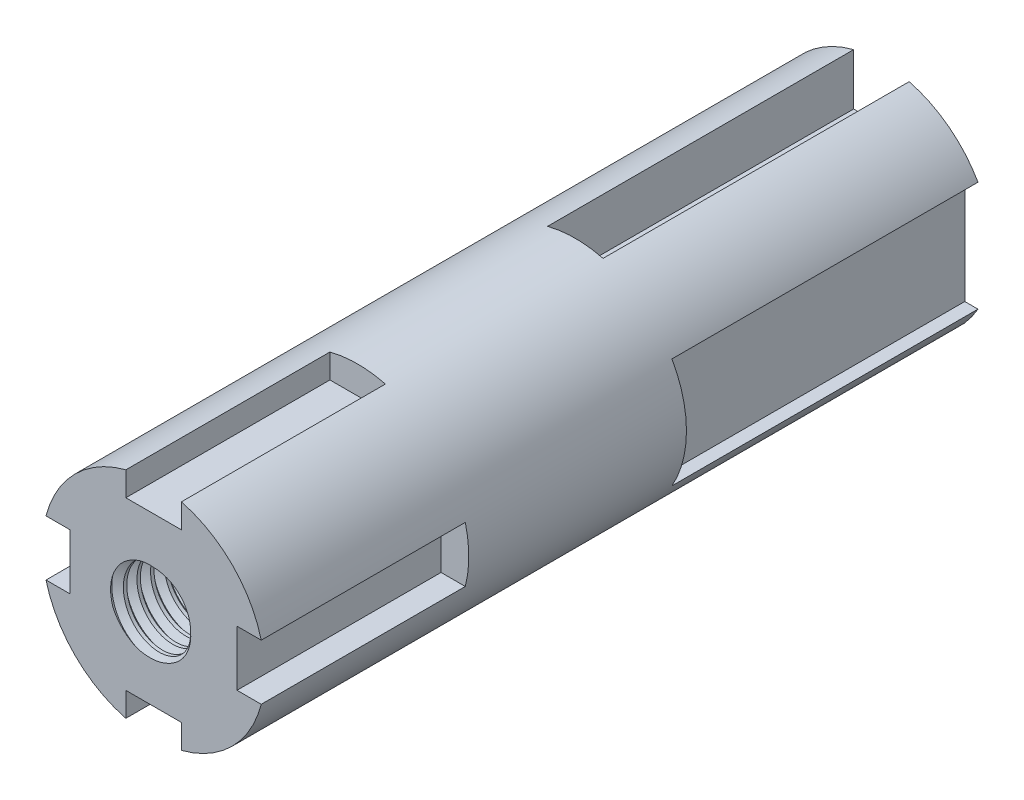
SolidWorks part; units mm, degrees
ref_plane "Front Plane" through (0, 0, 0) normal (0, 0, 1) x (1, 0, 0)
ref_plane "Top Plane" through (0, 0, 0) normal (0, 1, 0) x (1, 0, 0)
ref_plane "Right Plane" through (0, 0, 0) normal (1, 0, 0) x (0, 0, -1)
sketch "Sketch3" plane through (0, 0, 0) normal (0, 0, 1) x (1, 0, 0)
  circle A0 centre (0, 0) radius 4.085
  dimension "D1" = 8.17
extrude "Boss-Extrude2" add sketch "Sketch3" along normal blind 26.75
sketch "Sketch6" plane through (0, 0, 26.75) normal (0, 0, 1) x (1, 0, 0)
  line L10 (4.085, 1.02) -> (3.065, 1.02)
  line L11 (-1.02, 4.085) -> (1.02, 4.085)
  line L12 (-1.02, 4.085) -> (-1.02, 3.065)
  line L13 (-1.02, 3.065) -> (1.02, 3.065)
  line L14 (1.02, 4.085) -> (1.02, 3.065)
  line L15 (4.085, 1.02) -> (4.085, -1.02)
  line L16 (4.085, -1.02) -> (3.065, -1.02)
  line L17 (3.065, 1.02) -> (3.065, -1.02)
  line L18 (1.02, -4.085) -> (1.02, -3.065)
  line L19 (1.02, -4.085) -> (-1.02, -4.085)
  line L20 (-1.02, -4.085) -> (-1.02, -3.065)
  line L21 (1.02, -3.065) -> (-1.02, -3.065)
  line L22 (-4.085, -1.02) -> (-3.065, -1.02)
  line L23 (-4.085, -1.02) -> (-4.085, 1.02)
  line L24 (-4.085, 1.02) -> (-3.065, 1.02)
  line L25 (-3.065, -1.02) -> (-3.065, 1.02)
  circle A2 centre (0, 0) radius 4.085 construction
  point P4 (0, 4.085)
  point P23 (0, 0)
  dimension "D1" = 2.04
  dimension "D2" = 1.02
  dimension "D3" = 4
extrude "Cut-Extrude1" cut sketch "Sketch6" against normal blind 7.5
sketch "Sketch4" plane through (0, 0, 0) normal (0, 0, -1) x (-1, 0, 0)
  line L5 (-1.02, 2.065) -> (1.02, 2.065)
  line L6 (-1.02, 2.065) -> (-1.02, 4.085)
  line L7 (-1.02, 4.085) -> (1.02, 4.085)
  line L8 (1.02, 2.065) -> (1.02, 4.085)
  line L9 (-3.065, -2.02) -> (-4.085, -2.02)
  line L10 (-3.065, -2.02) -> (-3.065, 2.02)
  line L11 (-3.065, 2.02) -> (-4.085, 2.02)
  line L12 (-4.085, -2.02) -> (-4.085, 2.02)
  line L13 (-3.065, -2.02) -> (-4.085, 2.02) construction
  line L14 (-3.065, 2.02) -> (-4.085, -2.02) construction
  line L15 (3.065, -2.02) -> (4.085, -2.02)
  line L16 (3.065, -2.02) -> (3.065, 2.02)
  line L17 (3.065, 2.02) -> (4.085, 2.02)
  line L18 (4.085, -2.02) -> (4.085, 2.02)
  line L19 (3.065, -2.02) -> (4.085, 2.02) construction
  line L20 (3.065, 2.02) -> (4.085, -2.02) construction
  circle A2 centre (0, 0) radius 4.085 construction
  point P4 (0, 4.085)
  point P6 (-3.575, 0)
  point P13 (3.575, 0)
  dimension "D1" = 2.02
  dimension "D2" = 2.04
  dimension "D3" = 1.02
  dimension "D4" = 4.04
extrude "Cut-Extrude2" cut sketch "Sketch4" against normal blind 11.25
sketch "Sketch7" plane through (0, 0, 0) normal (0, 0, -1) x (-1, 0, 0)
  circle A0 centre (0, 0) radius 1.36
  dimension "D1" = 2.72
extrude "Cut-Extrude3" cut sketch "Sketch7" against normal blind 5
sketch "Sketch8" plane through (0, 0, 26.75) normal (0, 0, 1) x (1, 0, 0)
  circle A0 centre (0, 0) radius 1.36
  dimension "D1" = 2.72
extrude "Cut-Extrude4" cut sketch "Sketch8" against normal blind 5
thread "Thread1" pitch 0.5 method cut profile "Thread Profile1" start angle 0, offset 0, length 10, pitch 0.5, diameter 2.72
ref_plane "Plane1" through (-1.36, 0, 5) normal (0, -1, 0) x (-1, 0, 0)
sketch "Thread Profile1" plane through (-1.36, 0, 5) normal (0, -1, 0) x (-1, 0, 0)
  line L0 (0, 0) -> (0, 0.5) construction
  line L1 (0, 0) -> (0.2706, 0.1562)
  line L2 (0.2706, 0.1562) -> (0.2706, 0.2187)
  line L3 (0.2706, 0.2187) -> (0, 0.375)
  line L4 (0.2706, 0.1875) -> (0, 0.1875) construction
  line L11 (0, 0) -> (0, 0.375)
  point P2 (0, 0)
  dimension "Pitch" = 0.5
  dimension "Profile_Angle" = 60
  dimension "Profile_Land" = 0.0625
  dimension "Profile_Height" = 0.2706
thread "Thread2" pitch 0.5 method cut profile "Thread Profile2" start angle 0, offset 0, length 10, pitch 0.5, diameter 2.72
ref_plane "Plane2" through (1.36, 0, 21.75) normal (0, -1, 0) x (1, 0, 0)
sketch "Thread Profile2" plane through (1.36, 0, 21.75) normal (0, -1, 0) x (1, 0, 0)
  line L0 (0, 0) -> (0, 0.5) construction
  line L1 (0, 0) -> (0.2706, 0.1562)
  line L2 (0.2706, 0.1562) -> (0.2706, 0.2187)
  line L3 (0.2706, 0.2187) -> (0, 0.375)
  line L4 (0.2706, 0.1875) -> (0, 0.1875) construction
  line L11 (0, 0) -> (0, 0.375)
  point P2 (0, 0)
  dimension "Pitch" = 0.5
  dimension "Profile_Angle" = 60
  dimension "Profile_Land" = 0.0625
  dimension "Profile_Height" = 0.2706
equation "\"pin_diameter\"=8.17"
equation "\"pin_length\"=26.75"
equation "\"key_width\"=2.04"
equation "\"key_length\"=1.02"
equation "\"key_length_with_hump\"=2.02"
equation "\"key_width_with_offset\"=4.04"
equation "\"key_thickness\"=11.25"
equation "\"screw_diameter\"=2.72"
equation "\"D1@Sketch3\"=\"pin_diameter\""
equation "\"D1@Boss-Extrude2\"=\"pin_length\""
equation "\"D1@Sketch6\"=\"key_width\""
equation "\"D2@Sketch6\"=\"key_length\""
equation "\"D2@Sketch4\"=\"key_width\""
equation "\"D1@Sketch4\"=\"key_length_with_hump\""
equation "\"D4@Sketch4\"=\"key_width_with_offset\""
equation "\"D3@Sketch4\"=\"key_length\""
equation "\"D1@Cut-Extrude2\"=\"key_thickness\""
equation "\"D1@Sketch7\"=\"screw_diameter\""
equation "\"D1@Sketch8\"=\"screw_diameter\""
